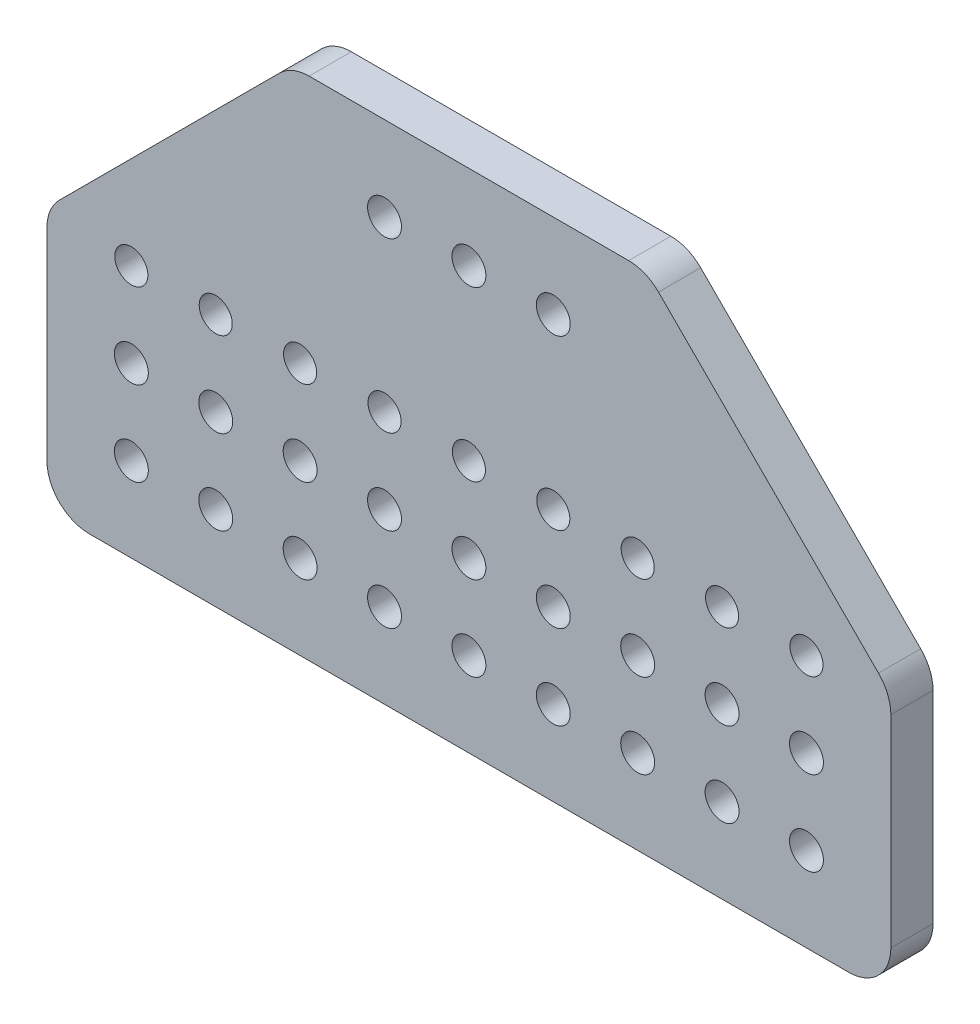
SolidWorks part; units mm, degrees
material "6061-T6 (SS)"
ref_plane "Front Plane" through (0, 0, 0) normal (0, 0, 1) x (1, 0, 0)
ref_plane "Top Plane" through (0, 0, 0) normal (0, 1, 0) x (1, 0, 0)
ref_plane "Right Plane" through (0, 0, 0) normal (1, 0, 0) x (0, 0, -1)
sketch "Sketch1" plane through (0, 0, 0) normal (0, 0, 1) x (1, 0, 0)
  line L1 (0, 0) -> (127, 0)
  line L2 (0, 0) -> (0, 82.55)
  line L3 (0, 82.55) -> (127, 82.55)
  line L4 (127, 0) -> (127, 82.55)
  dimension "D1" = 82.55
  dimension "D2" = 127
extrude "Boss-Extrude1" add sketch "Sketch1" along normal blind 6.35
sketch "Sketch2" plane through (0, 0, 0) normal (0, 0, -1) x (-1, 0, 0)
  line L0 (-127, 82.55) -> (0, 82.55) construction
  line L1 (0, 82.55) -> (0, 0) construction
  circle A0 centre (-76.2, 63.5) radius 2.5527
  circle A1 centre (-63.5, 63.5) radius 2.5527
  circle A2 centre (-50.8, 63.5) radius 2.5527
  dimension "D2" = 12.7
  dimension "D3" = 12.7
  dimension "D4" = 50.8
  dimension "D5" = 19.05
  dimension "D7" = 5.1054
  dimension "D8" = 5.1054
  dimension "D9" = 5.1054
extrude "Cut-Extrude1" cut sketch "Sketch2" against normal through all and the other way through all
sketch "Sketch3" plane through (0, 0, 0) normal (0, 0, -1) x (-1, 0, 0)
  line L0 (-127, 0) -> (-127, 82.55) construction
  line L1 (0, 0) -> (-127, 0) construction
  circle A0 centre (-114.3, 38.1) radius 2.4892
  circle A1 centre (-114.3, 25.4) radius 2.5527
  circle A2 centre (-114.3, 12.7) radius 2.5527
  circle A3 centre (-101.6, 38.1) radius 2.4892
  circle A4 centre (-101.6, 25.4) radius 2.5527
  circle A5 centre (-101.6, 12.7) radius 2.5527
  circle A6 centre (-88.9, 38.1) radius 2.4892
  circle A7 centre (-88.9, 25.4) radius 2.5527
  circle A8 centre (-88.9, 12.7) radius 2.5527
  circle A9 centre (-76.2, 38.1) radius 2.4892
  circle A10 centre (-76.2, 25.4) radius 2.5527
  circle A11 centre (-76.2, 12.7) radius 2.5527
  circle A12 centre (-63.5, 38.1) radius 2.4892
  circle A13 centre (-63.5, 25.4) radius 2.5527
  circle A14 centre (-63.5, 12.7) radius 2.5527
  circle A15 centre (-50.8, 38.1) radius 2.4892
  circle A16 centre (-50.8, 25.4) radius 2.5527
  circle A17 centre (-50.8, 12.7) radius 2.5527
  circle A18 centre (-38.1, 38.1) radius 2.4892
  circle A19 centre (-38.1, 25.4) radius 2.5527
  circle A20 centre (-38.1, 12.7) radius 2.5527
  circle A21 centre (-25.4, 38.1) radius 2.4892
  circle A22 centre (-25.4, 25.4) radius 2.5527
  circle A23 centre (-25.4, 12.7) radius 2.5527
  circle A24 centre (-12.7, 38.1) radius 2.4892
  circle A25 centre (-12.7, 25.4) radius 2.5527
  circle A26 centre (-12.7, 12.7) radius 2.5527
  dimension "D1" = 4.9784
  dimension "D2" = 5.1054
  dimension "D3" = 5.1054
  dimension "D4" = 12.7
  dimension "D5" = 12.7
  dimension "D6" = 12.7
  dimension "D7" = 12.7
  dimension "D8" = 12.7
  dimension "D9" = 12.7
  dimension "D11" = 12.7
  dimension "D10" = 9
extrude "Cut-Extrude2" cut sketch "Sketch3" against normal through all
sketch "Sketch4" plane through (0, 0, 0) normal (0, 0, -1) x (-1, 0, 0)
  line L0 (-83.82, 82.55) -> (-127, 39.37)
  line L1 (-127, 82.55) -> (0, 82.55) construction
  line L2 (-127, 39.37) -> (-127, 82.55)
  line L3 (-127, 82.55) -> (-83.82, 82.55)
  line L4 (-43.18, 82.55) -> (0, 82.55)
  line L5 (0, 82.55) -> (0, 39.37)
  line L6 (0, 82.55) -> (0, 0) construction
  line L7 (0, 39.37) -> (-43.18, 82.55)
  dimension "D1" = 45
  dimension "D2" = 45
  dimension "D3" = 43.18
  dimension "D4" = 43.18
extrude "Cut-Extrude3" cut sketch "Sketch4" against normal through all
sketch "Sketch5" plane through (0, 0, 0) normal (0, 0, -1) x (-1, 0, 0)
  line L0 (-90.17, 76.2) -> (-36.83, 76.2)
  line L1 (-127, 39.37) -> (-83.82, 82.55) construction
  line L2 (-43.18, 82.55) -> (0, 39.37) construction
  line L3 (-36.83, 76.2) -> (-43.18, 82.55)
  line L4 (-43.18, 82.55) -> (-83.82, 82.55)
  line L5 (-83.82, 82.55) -> (-90.17, 76.2)
  dimension "D1" = 6.35
extrude "Cut-Extrude4" cut sketch "Sketch5" against normal through all
fillet "Fillet1" radius 6.35 6 edges at (127, 39.37, 3.175) (127, 0, 3.175) (0, 0, 3.175) (36.83, 76.2, 3.175) (90.17, 76.2, 3.175) (0, 39.37, 3.175)
